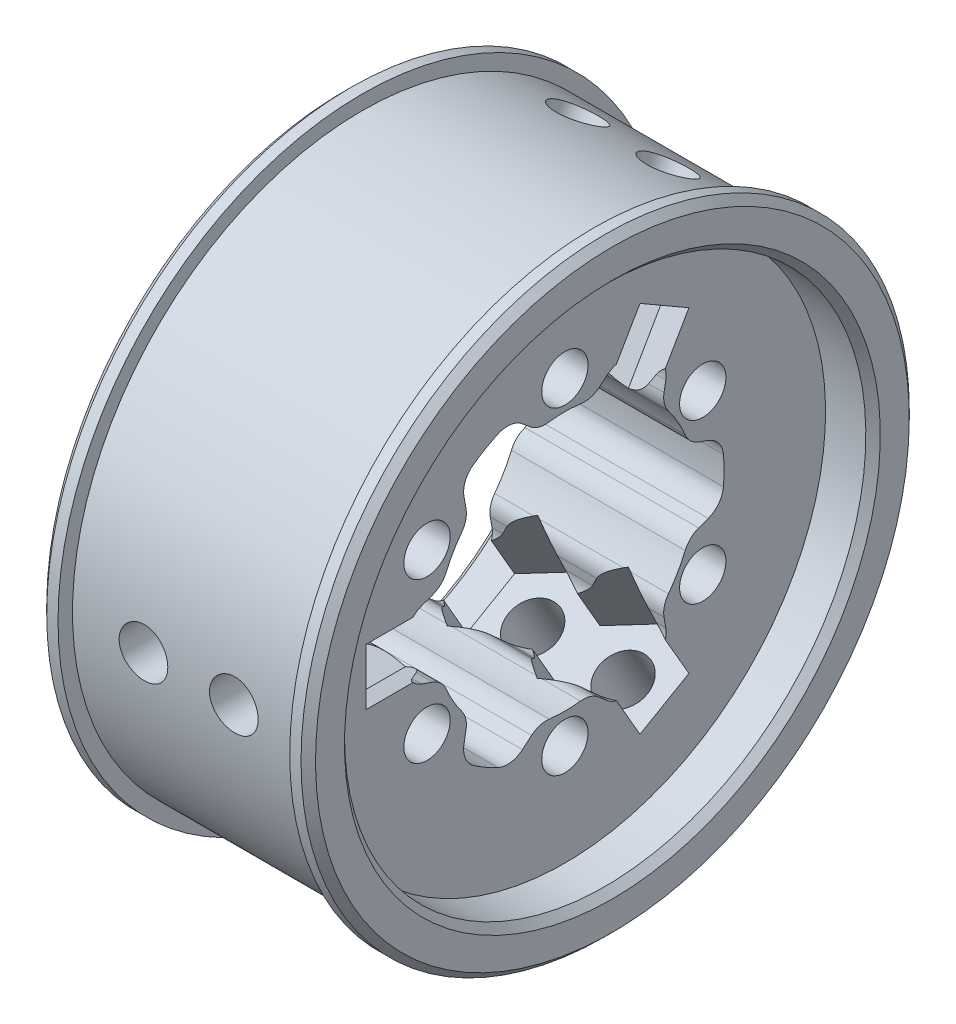
SolidWorks part; units mm, degrees
ref_plane "Front Plane" through (0, 0, 0) normal (0, 0, 1) x (1, 0, 0)
ref_plane "Top Plane" through (0, 0, 0) normal (0, 1, 0) x (1, 0, 0)
ref_plane "Right Plane" through (0, 0, 0) normal (1, 0, 0) x (0, 0, -1)
sketch "Sketch1" plane through (0, 0, 0) normal (0, 0, 1) x (1, 0, 0)
  line L0 (0, 0) -> (0, 31.75)
  line L1 (0, 31.75) -> (12.7, 31.75)
  line L2 (12.7, 31.75) -> (12.7, 33.3375)
  line L3 (12.7, 33.3375) -> (14.732, 33.3375)
  line L4 (14.732, 33.3375) -> (14.732, 0)
  line L5 (14.732, 0) -> (0, 0)
  dimension "D1" = 12.7
  dimension "D2" = 2.032
  dimension "D3" = 1.5875
  dimension "D4" = 31.75
revolve "Revolve1" add sketch "Sketch1" angle 360 about L5
sketch "Sketch2" plane through (14.732, 0, 0) normal (1, 0, 0) x (0, 0, -1)
  line L0 (14.6656, 4.0824) -> (15.7207, 3.6983)
  line L1 (14.6656, -4.0824) -> (15.7207, -3.6983)
  line L2 (0, 0) -> (25.6394, 0) construction
  line L3 (3.6486, -14.6171) -> (4.6575, -15.4637)
  line L4 (10.8682, -10.6596) -> (11.0632, -11.7654)
  line L5 (-10.8345, -10.4683) -> (-11.0632, -11.7654)
  line L6 (-3.6486, -14.6171) -> (-4.6575, -15.4637)
  line L7 (-14.4831, 4.1488) -> (-15.7207, 3.6983)
  line L8 (-14.4831, -4.1488) -> (-15.7207, -3.6983)
  line L9 (-3.7974, 14.7419) -> (-4.6575, 15.4637)
  line L10 (-10.8345, 10.4683) -> (-11.0632, 11.7654)
  line L11 (10.8682, 10.6596) -> (11.0632, 11.7654)
  line L12 (3.7974, 14.7419) -> (4.6575, 15.4637)
  circle A0 centre (0, 0) radius 17.4498 construction
  circle A1 centre (0, 17.4498) radius 2.54
  circle A2 centre (15.112, 8.7249) radius 2.54
  circle A3 centre (15.112, -8.7249) radius 2.54
  circle A4 centre (0, -17.4498) radius 2.54
  circle A5 centre (-15.112, -8.7249) radius 2.54
  circle A6 centre (-15.112, 8.7249) radius 2.54
  circle A7 centre (0, 0) radius 14.2875 construction
  arc A9 (17.3822, 1.5349) -> (17.3822, -1.5349) centre (0, 0) cw
  arc A11 (10.0204, -14.2859) -> (7.3618, -15.8209) centre (0, 0) cw
  arc A12 (-7.3618, -15.8209) -> (-10.0204, -14.2859) centre (0, 0) cw
  arc A13 (-17.3822, -1.5349) -> (-17.3822, 1.5349) centre (0, 0) cw
  arc A14 (-10.0204, 14.2859) -> (-7.3618, 15.8209) centre (0, 0) cw
  arc A15 (7.3618, 15.8209) -> (10.0204, 14.2859) centre (0, 0) cw
  arc A16 (11.3516, -8.6761) -> (13.1895, -5.4927) centre (0, 0) ccw
  arc A18 (-1.709, -14.0414) -> (1.709, -14.0414) centre (0, 0) ccw
  arc A19 (-13.0148, -5.5407) -> (-11.3057, -8.5008) centre (0, 0) ccw
  arc A20 (-11.3057, 8.5008) -> (-13.0148, 5.5407) centre (0, 0) ccw
  arc A21 (1.8379, 14.1688) -> (-1.8379, 14.1688) centre (0, 0) ccw
  arc A22 (13.1895, 5.4927) -> (11.3516, 8.6761) centre (0, 0) ccw
  arc A23 (13.1895, 5.4927) -> (14.6656, 4.0824) centre (15.5343, 6.4692) ccw
  arc A24 (11.3516, 8.6761) -> (10.8682, 10.6596) centre (13.3696, 10.2185) cw
  arc A25 (11.0632, 11.7654) -> (10.0204, 14.2859) centre (8.5618, 12.2065) ccw
  arc A26 (7.3618, 15.8209) -> (4.6575, 15.4637) centre (6.2902, 13.518) ccw
  arc A27 (3.7974, 14.7419) -> (1.8379, 14.1688) centre (2.1647, 16.6877) cw
  arc A28 (-1.8379, 14.1688) -> (-3.7974, 14.7419) centre (-2.1647, 16.6877) cw
  arc A29 (-4.6575, 15.4637) -> (-7.3618, 15.8209) centre (-6.2902, 13.518) ccw
  arc A30 (-10.0204, 14.2859) -> (-11.0632, 11.7654) centre (-8.5618, 12.2065) ccw
  arc A31 (-10.8345, 10.4683) -> (-11.3057, 8.5008) centre (-13.3359, 10.0272) cw
  arc A32 (-13.0148, 5.5407) -> (-14.4831, 4.1488) centre (-15.3518, 6.5356) cw
  arc A33 (-15.7207, 3.6983) -> (-17.3822, 1.5349) centre (-14.852, 1.3115) ccw
  arc A34 (-17.3822, -1.5349) -> (-15.7207, -3.6983) centre (-14.852, -1.3115) ccw
  arc A35 (-14.4831, -4.1488) -> (-13.0148, -5.5407) centre (-15.3518, -6.5356) cw
  arc A36 (-11.3057, -8.5008) -> (-10.8345, -10.4683) centre (-13.3359, -10.0272) cw
  arc A37 (-11.0632, -11.7654) -> (-10.0204, -14.2859) centre (-8.5618, -12.2065) ccw
  arc A38 (-7.3618, -15.8209) -> (-4.6575, -15.4637) centre (-6.2902, -13.518) ccw
  arc A39 (-3.6486, -14.6171) -> (-1.709, -14.0414) centre (-2.0159, -16.5628) cw
  arc A40 (1.709, -14.0414) -> (3.6486, -14.6171) centre (2.0159, -16.5628) cw
  arc A41 (4.6575, -15.4637) -> (7.3618, -15.8209) centre (6.2902, -13.518) ccw
  arc A42 (10.0204, -14.2859) -> (11.0632, -11.7654) centre (8.5618, -12.2065) ccw
  arc A43 (10.8682, -10.6596) -> (11.3516, -8.6761) centre (13.3696, -10.2185) cw
  arc A44 (13.1895, -5.4927) -> (14.6656, -4.0824) centre (15.5343, -6.4692) cw
  arc A45 (15.7207, -3.6983) -> (17.3822, -1.5349) centre (14.852, -1.3115) ccw
  arc A46 (17.3822, 1.5349) -> (15.7207, 3.6983) centre (14.852, 1.3115) ccw
  point P18 (0, 0)
  point P45 (0, 0)
  point P52 (13.5661, 4.4825)
  point P61 (2.9011, 13.9899)
  point P92 (13.5661, -4.4825)
  point P95 (17.1585, -3.175)
  point P98 (17.1585, 3.175)
  dimension "D1" = 34.8996
  dimension "D2" = 5.08
  dimension "D4" = 28.575
  dimension "D5" = 20
  dimension "D7" = 6.35
  dimension "D9" = 2.54
  dimension "D10" = 2.54
  dimension "D6" = 20
  dimension "D3" = 6
  dimension "D8" = 6
mirror "Mirror3" about plane through (0, 0, 0) normal (-1, 0, 0) of "Revolve1"
extrude "Cut-Extrude3" cut sketch "Sketch2" against normal through all
sketch "Sketch3" plane through (14.732, 0, 0) normal (1, 0, 0) x (0, 0, -1)
  circle A0 centre (0, 0) radius 28.575
  dimension "D1" = 57.15
extrude "Cut-Extrude4" cut sketch "Sketch3" against normal blind 5.207
sketch "Sketch4" plane through (-14.732, 0, 0) normal (-1, 0, 0) x (0, 0, 1)
  circle A0 centre (0, 0) radius 22.86
  dimension "D1" = 45.72
extrude "Cut-Extrude5" cut sketch "Sketch4" against normal blind 5.207 contours A0
chamfer "Chamfer1" distance 0.7937 angle 45 4 edges at (-14.732, -22.86, 0) (-14.732, 33.3375, 0) (14.732, 33.3375, 0) (14.732, 28.575, 0)
ref_plane "Plane2" through (0, 0, 17.3822) normal (0, 0, 1) x (1, 0, 0)
ref_plane "Plane3" through (0, -15.0534, 8.6911) normal (0, -0.866, 0.5) x (-1, 0, 0)
sketch "Sketch7" plane through (0, 0, 17.3822) normal (0, 0, 1) x (1, 0, 0)
  line L1 (-4.9213, 5.6826) -> (-9.8425, 2.8413)
  line L2 (-9.8425, 2.8413) -> (-9.8425, -2.8413)
  line L3 (-9.8425, -2.8413) -> (-4.9212, -5.6826)
  line L4 (-4.9212, -5.6826) -> (0, -2.8413)
  line L6 (0, 2.8413) -> (-4.9213, 5.6826)
  line L7 (4.9848, 5.7192) -> (0, 2.8413)
  line L9 (0, -2.8413) -> (4.9848, -5.7192)
  line L10 (4.9848, -5.7192) -> (9.9378, -2.8596)
  line L11 (9.9378, -2.8596) -> (9.9377, 2.8596)
  line L12 (9.9377, 2.8596) -> (4.9848, 5.7192)
  line L13 (-9.525, 1.5349) -> (-9.525, -1.5349) construction
  line L14 (9.525, -1.5349) -> (-9.525, -1.5349) construction
  line L15 (0, -2.9139) -> (0, 2.8053) [skipped]
  line L16 (0.0318, 2.8596) -> (0.0318, -2.8596) [skipped]
  circle A0 centre (-4.9213, 0) radius 4.9212 construction
  circle A1 centre (4.9848, 0) radius 4.953 construction
  point P12 (0, -1.5349)
  point P23 (-9.525, 0)
  dimension "D1" = 9.906
  dimension "D2" = 9.906
extrude "Cut-Extrude6" cut sketch "Sketch7" along normal blind 9.525 from offset 5.08 offset against normal yes
sketch "Sketch10" plane through (0, 0, 21.8272) normal (0, 0, -1) x (-1, 0, 0)
  line L0 (-4.9848, 5.7192) -> (-4.9848, -5.7192) construction
  line L1 (4.9213, 5.6826) -> (4.9212, -5.6826) construction
  circle A0 centre (-4.9848, 0) radius 2.667
  circle A1 centre (4.9213, 0) radius 2.667
  dimension "D1" = 5.334
extrude "Cut-Extrude9" cut sketch "Sketch10" against normal through all
ref_plane "Plane4" through (0, -7.0207, 12.1603) normal (0, -0.5, 0.866) x (1, 0, 0)
sketch "Sketch11" plane through (0, -21.2872, -2.1063) normal (0, 0.866, -0.5) x (1, 0, 0)
  line L0 (11.6525, -12.4677) -> (-11.6712, -12.4677) construction
  line L4 (-12.7, -44.2177) -> (-12.7, 19.2823) construction
  line L5 (12.7, 19.2823) -> (12.7, -44.2177) construction
  circle A0 centre (-7.9375, -6.1177) radius 1.0922
  circle A1 centre (-7.9375, -18.8177) radius 1.0922
  circle A2 centre (7.9375, -18.8177) radius 1.0922
  circle A3 centre (7.9375, -6.1177) radius 1.0922
  dimension "D1" = 2.1844
  dimension "D2" = 4.7625
  dimension "D3" = 4.7625
  dimension "D5" = 6.35
  dimension "D6" = 6.35
pattern_circular "CirPattern2" count 3 every 120 about axis through (12.7, 0, 0) along (1, 0, 0) of "Cut-Extrude9", "Cut-Extrude6"
extrude "Cut-Extrude10" cut sketch "Sketch11" against normal through all
ref_plane "Plane5" through (0, -1.5315, 0.8936) normal (0, -0.8637, 0.504) x (-1, 0, 0)
